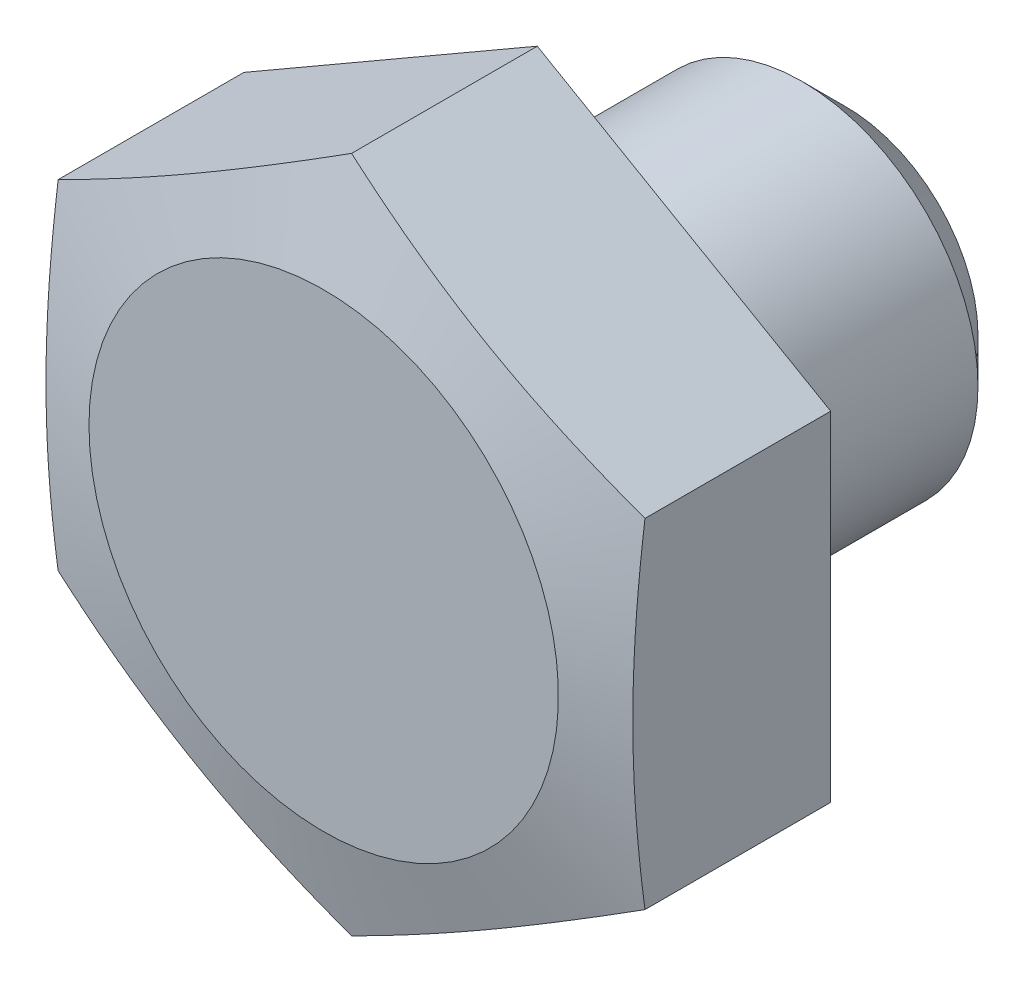
SolidWorks part; units mm, degrees
ref_plane "前视基准面" through (0, 0, 0) normal (0, 0, 1) x (1, 0, 0)
ref_plane "上视基准面" through (0, 0, 0) normal (0, 1, 0) x (1, 0, 0)
ref_plane "右视基准面" through (0, 0, 0) normal (1, 0, 0) x (0, 0, -1)
sketch "草图1" plane through (0, 0, 0) normal (0, 0, 1) x (1, 0, 0)
  line L1 (0, 5.7735) -> (-5, 2.8868)
  line L2 (-5, 2.8868) -> (-5, -2.8868)
  line L3 (-5, -2.8868) -> (0, -5.7735)
  line L4 (0, -5.7735) -> (5, -2.8868)
  line L5 (5, -2.8868) -> (5, 2.8868)
  line L6 (5, 2.8868) -> (0, 5.7735)
  circle A0 centre (0, 0) radius 5 construction
  dimension "s" = 10
extrude "凸台-拉伸1" add sketch "草图1" along normal blind 3.9
sketch "草图2" plane through (0, 0, 0) normal (0, 0, 1) x (1, 0, 0)
  circle A0 centre (0, 0) radius 4.5
  dimension "D1" = 9
ref_axis "基准轴1" through (0, 0, 0) along (0, 0, -1)
sketch "草图3" plane through (0, 0, 0) normal (0, 0, 1) x (1, 0, 0)
  circle A0 centre (0, 0) radius 3
  dimension "d" = 6
extrude "凸台-拉伸3" add sketch "草图3" against normal blind 5
cosmetic thread "装饰螺纹线1" parameters "D2"=2.459
sketch "草图4" plane through (0, 0, 0) normal (1, 0, 0) x (0, 0, -1)
  line L0 (2.242, 0) -> (-1.4572, 0) construction
  line L2 (-3.9, 20) -> (-3.9, 4)
  line L3 (-3.9, 20) -> (0.3872, 20)
  line L6 (-3.9, 2.8868) -> (-3.9, 5.7735) construction
  line L7 (-3.9, 4) -> (0.3872, 20)
  dimension "D3" = 20
  dimension "D2" = 4
  dimension "D1" = 15
revolve "切除-旋转1" cut sketch "草图4" angle 360 about L0
chamfer "倒角1" distance 0.75 angle 45 1 edges at (3, 0, -5)
extrude "切除-拉伸1" cut sketch "草图2" along normal blind 0.26 flip side to cut contours A0
fillet "圆角1" radius 0.1 1 edges at (3, 0, 0)
ref_plane "基准面1" through (0, 0, 0) normal (0, 0, -1) x (-1, 0, 0)
equation "\"D2@草图4\"=\"s@草图1\" * 0.4"
equation "\"D3@草图4\"=\"s@草图1\" * 2"
equation "\"D1@倒角1\"=\"d@草图3\" / 8"
equation "\"D1@草图2\"=\"s@草图1\"*0.9"
equation "\"D1@切除-拉伸1\" = \"k@凸台-拉伸1\" / 15"
